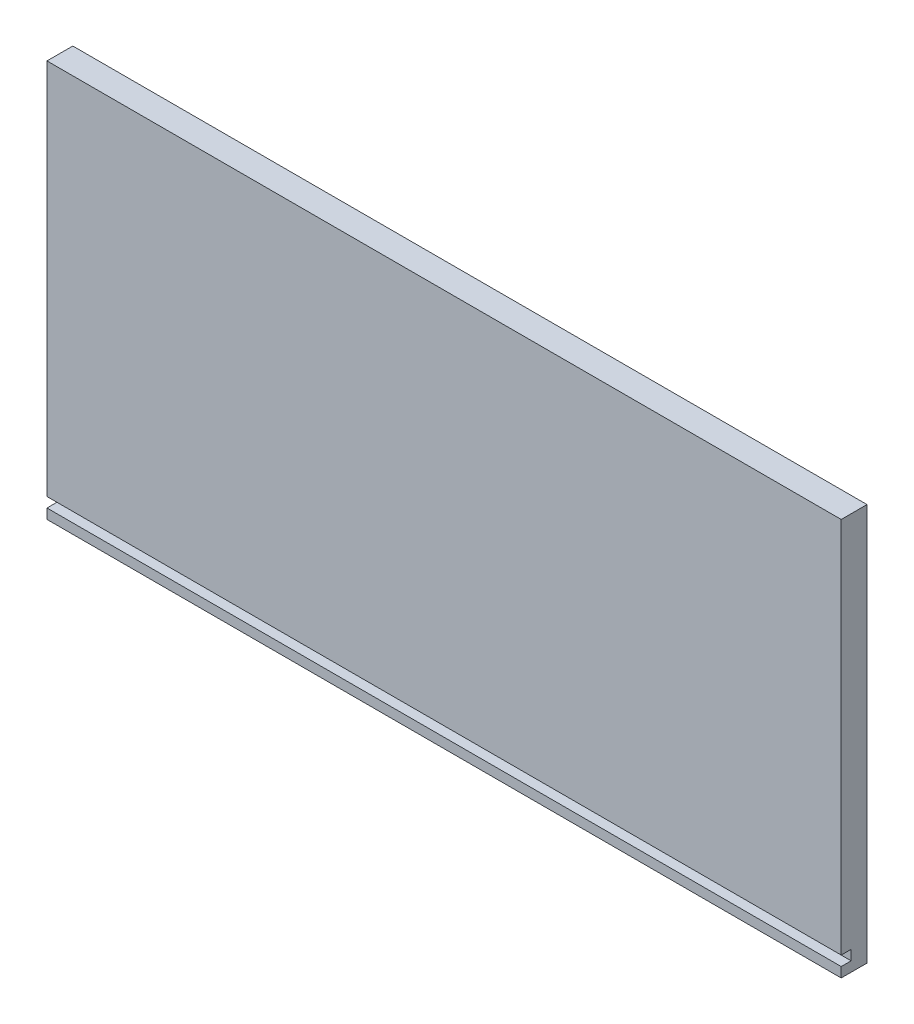
SolidWorks part; units mm, degrees
ref_plane "正面" through (0, 0, 0) normal (0, 0, 1) x (1, 0, 0)
ref_plane "平面" through (0, 0, 0) normal (0, 1, 0) x (1, 0, 0)
ref_plane "右側面" through (0, 0, 0) normal (1, 0, 0) x (0, 0, -1)
sketch "ｽｹｯﾁ1" plane through (0, 0, 0) normal (0, 0, 1) x (1, 0, 0)
  line L1 (-69.2801, 161.5071) -> (330.7199, 161.5071)
  line L2 (-69.2801, 161.5071) -> (-69.2801, -38.4929)
  line L3 (-69.2801, -38.4929) -> (330.7199, -38.4929)
  line L4 (330.7199, 161.5071) -> (330.7199, -38.4929)
  dimension "D1" = 400
  dimension "D3" = 200
extrude "ﾎﾞｽ - 押し出し1" add sketch "ｽｹｯﾁ1" along normal blind 13
sketch "ｽｹｯﾁ2" plane through (0, 0, 13) normal (0, 0, 1) x (1, 0, 0)
  line L0 (330.7199, -38.4929) -> (330.7199, 161.5071) construction
  line L1 (330.7199, -33.4929) -> (-69.2801, -33.4929)
  line L2 (330.7199, -33.4929) -> (330.7199, -28.4929)
  line L3 (330.7199, -28.4929) -> (-69.2801, -28.4929)
  line L4 (-69.2801, -33.4929) -> (-69.2801, -28.4929)
  line L5 (-69.2801, 161.5071) -> (-69.2801, -38.4929) construction
  line L7 (-69.2801, -38.4929) -> (330.7199, -38.4929) construction
  dimension "D1" = 5
  dimension "D2" = 400
  dimension "D3" = 5
extrude "ｶｯﾄ - 押し出し1" cut sketch "ｽｹｯﾁ2" against normal blind 5
